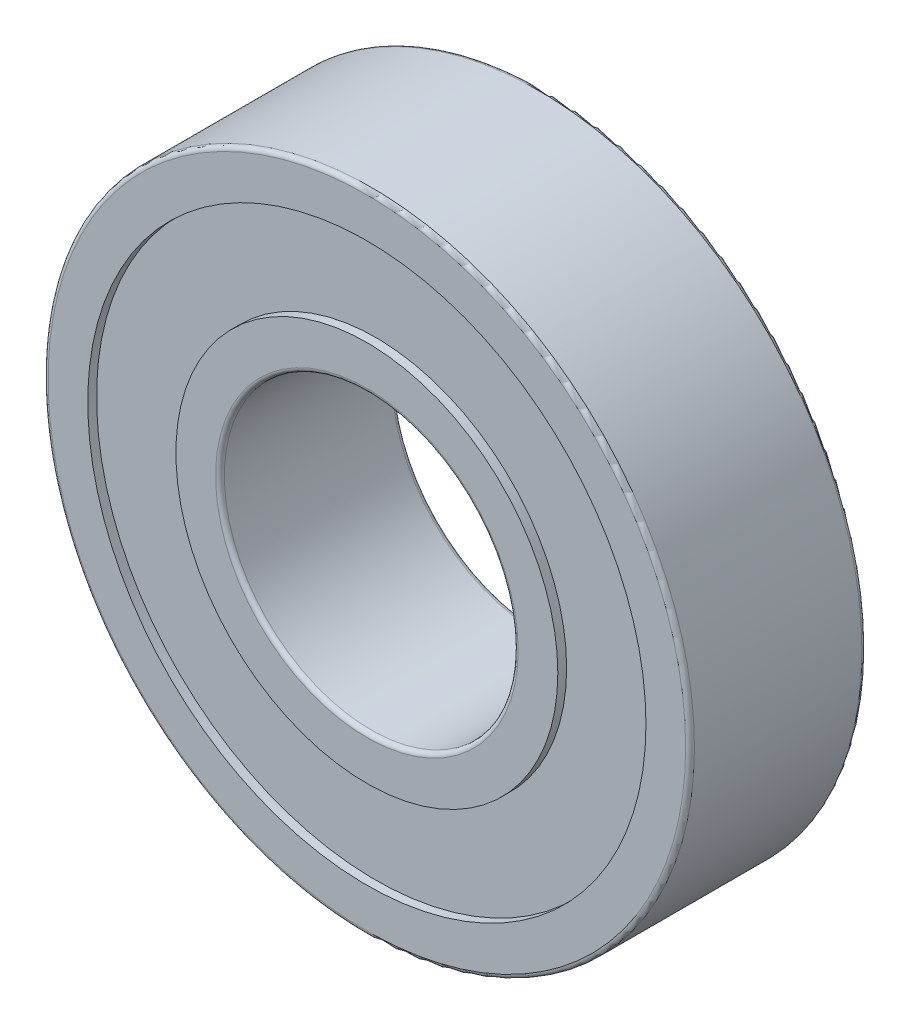
SolidWorks part; units mm, degrees
ref_plane "Front Plane" through (0, 0, 0) normal (0, 0, 1) x (1, 0, 0)
ref_plane "Top Plane" through (0, 0, 0) normal (0, 1, 0) x (1, 0, 0)
ref_plane "Right Plane" through (0, 0, 0) normal (1, 0, 0) x (0, 0, -1)
sketch "Sketch1" plane through (0, 0, 0) normal (0, 0, 1) x (1, 0, 0)
  circle A0 centre (0, 0) radius 5
  circle A1 centre (0, 0) radius 11
  dimension "D1" = 10
  dimension "D2" = 22
extrude "Boss-Extrude1" add sketch "Sketch1" along normal blind 6
sketch "Sketch2" plane through (0, 0, 6) normal (0, 0, 1) x (1, 0, 0)
  circle A3 centre (0, 0) radius 9.5
  circle A6 centre (0, 0) radius 6.5
  dimension "D1" = 13
  dimension "D2" = 19
extrude "Cut-Extrude1" cut sketch "Sketch2" against normal blind 0.3
extrude "Cut-Extrude2" cut sketch "Sketch2<2>" along normal blind 0.5 from surface starting at face at (11, 0, 0)
sketch "Sketch2<2>" plane through (0, 0, 6) normal (0, 0, 1) x (1, 0, 0) same geometry as "Sketch2"
fillet "Fillet1" radius 0.15 4 edges at (5, 0, 6) (11, 0, 6) (5, 0, 0) (11, 0, 0)
